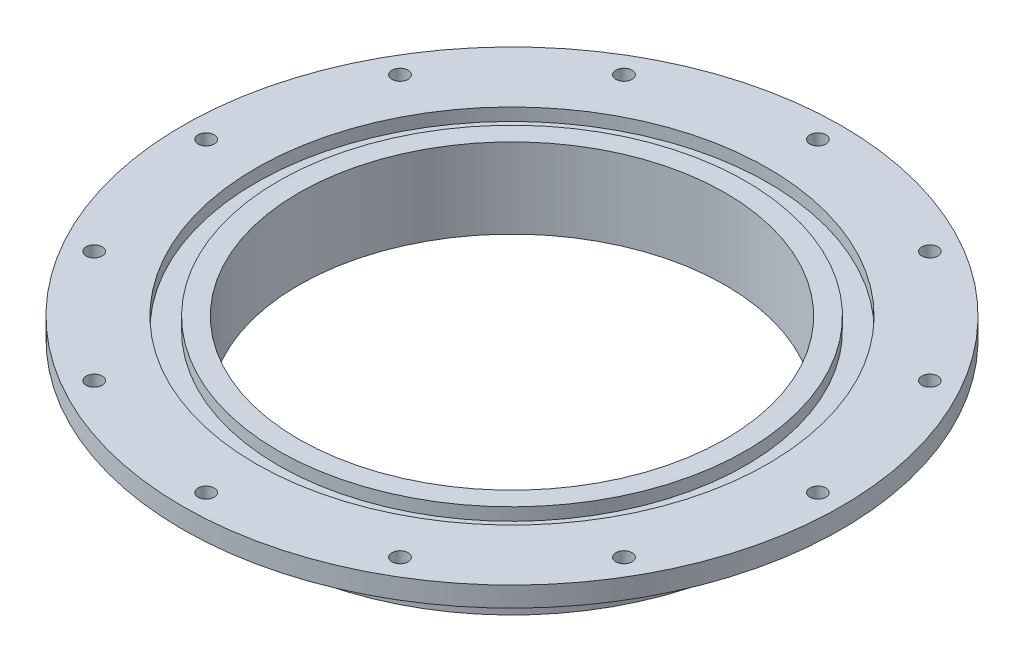
SolidWorks part; units mm, degrees
ref_plane "Front Plane" through (0, 0, 0) normal (0, 0, 1) x (1, 0, 0)
ref_plane "Top Plane" through (0, 0, 0) normal (0, 1, 0) x (1, 0, 0)
ref_plane "Right Plane" through (0, 0, 0) normal (1, 0, 0) x (0, 0, -1)
sketch "Sketch1" plane through (0, 0, 0) normal (0, 1, 0) x (1, 0, 0)
  circle A0 centre (0, 0) radius 80.518
  circle A1 centre (0, 0) radius 67.818
  dimension "D1" = 161.036
  dimension "D2" = 12.7
extrude "Inner Cylinder" add sketch "Sketch1" along normal blind 19.05
sketch "Sketch2" plane through (0, 19.05, 0) normal (0, 1, 0) x (1, 0, 0)
  circle A0 centre (0, 0) radius 67.818
  circle A1 centre (0, 0) radius 67.818 construction
  circle A2 centre (0, 0) radius 104.775
  dimension "D1" = 209.55
extrude "Flange" add sketch "Sketch2" along normal blind 6.35
sketch "Sketch4" plane through (0, 25.4, 0) normal (0, 1, 0) x (1, 0, 0)
  line L0 (0, 75.8825) -> (0, 81.2165) construction
  circle A3 centre (0, 0) radius 81.407
  circle A4 centre (0, 0) radius 74.295
  point P7 (0, 78.5495)
  dimension "D1" = 148.59
  dimension "D2" = 7.112
  dimension "D3" = 2.667
extrude "Groove" cut sketch "Sketch4" against normal blind 3.9878
sketch "Sketch5" plane through (0, 25.4, 0) normal (0, 1, 0) x (1, 0, 0)
  line L0 (89.7255, 0) -> (104.775, 0) construction
  circle A0 centre (0, 0) radius 97.2503 construction
  circle A1 centre (0, -97.2503) radius 3.175 construction
  circle A3 centre (0, -97.2503) radius 2.5527
  circle A6 centre (0, 0) radius 89.7255 construction
  circle A7 centre (0, 0) radius 104.775 construction
  point P9 (97.2503, 0)
  dimension "D1" = 5.1054
  dimension "D2" = 179.451
  dimension "D3" = 6.35
extrude "Screw Holes" cut sketch "Sketch5" against normal up to surface (6.35 mm away) up to face at (0, 19.05, 80.518)
pattern_circular "CirPattern1" count 12 over 360 about axis through (0, 25.4, 0) along (0, 1, 0) of "Screw Holes"
sketch "Tube OD Reference" plane through (0, 25.4, 0) normal (0, 1, 0) x (1, 0, 0)
  circle A0 centre (0, 0) radius 89.7255
  dimension "D1" = 179.451
ref_plane "Plane1" through (0, 9.525, 0) normal (0, -1, 0) x (-1, 0, 0)
sketch "Sketch7" plane through (0, 9.525, 0) normal (0, -1, 0) x (-1, 0, 0)
  circle A0 centre (0, 0) radius 80.518
  circle A1 centre (0, 0) radius 80.518 construction
  circle A2 centre (0, 0) radius 76.1746
  dimension "D1" = 4.3434
extrude "Cut-Extrude1" cut sketch "Sketch7" against normal blind 3.6068 and the other way blind 3.6068
